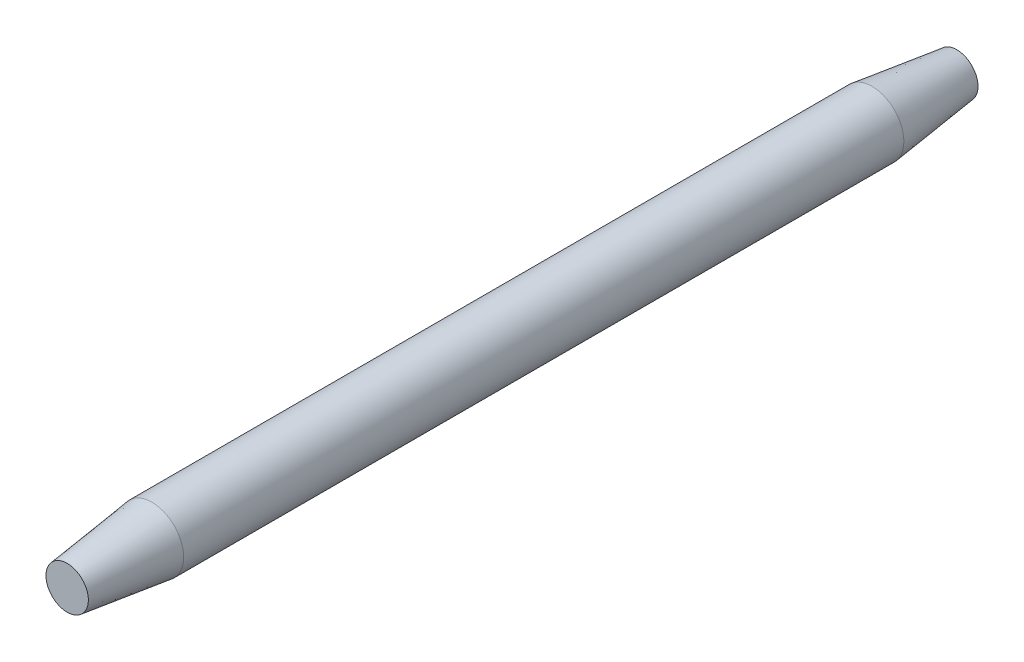
SolidWorks part; units mm, degrees
material "HYPALON"
ref_plane "Front Plane" through (0, 0, 0) normal (0, 0, 1) x (1, 0, 0)
ref_plane "Top Plane" through (0, 0, 0) normal (0, 1, 0) x (1, 0, 0)
ref_plane "Right Plane" through (0, 0, 0) normal (1, 0, 0) x (0, 0, -1)
sketch "Section" plane through (0, 0, 0) normal (0, 0, 1) x (1, 0, 0)
  circle A0 centre (0, 0) radius 150
  dimension "D1" = 300
extrude "Boss-Extrude1" add sketch "Section" along normal blind 3400 contours A0
sketch "ConoProa" plane through (0, 0, 0) normal (1, 0, 0) x (0, 0, -1)
  line L4 (-3400, 0) -> (-3800, 0) construction
  line L5 (-3400, 150) -> (-3400, -150) construction
  line L6 (-3800, 0) -> (-3800, 100)
  line L7 (-3800, 100) -> (-3400, 150)
  line L8 (-3400, 150) -> (-3400, 0)
  line L9 (-3400, 0) -> (-3800, 0)
  dimension "D1" = 100
  dimension "D2" = 400
sketch "ConoPopa" plane through (0, 0, 0) normal (1, 0, 0) x (0, 0, -1)
  line L0 (0, 0) -> (400, 0) construction
  line L1 (0, -150) -> (0, 150) construction
  line L2 (400, 0) -> (400, 100)
  line L3 (400, 100) -> (0, 150)
  line L4 (0, 150) -> (0, 0)
  line L5 (0, 0) -> (400, 0)
  dimension "D1" = 400
  dimension "D2" = 100
revolve "Revolve1" add sketch "ConoPopa" angle 360 about L0
revolve "Revolve2" add sketch "ConoProa" angle 360 about L4
ref_axis "Axis1" through (0, 0, 3400) along (0, 0, -1)
ref_plane "TopSupportTangentPlane" through (0, 150, 0) normal (0, 1, 0) x (1, 0, 0)
